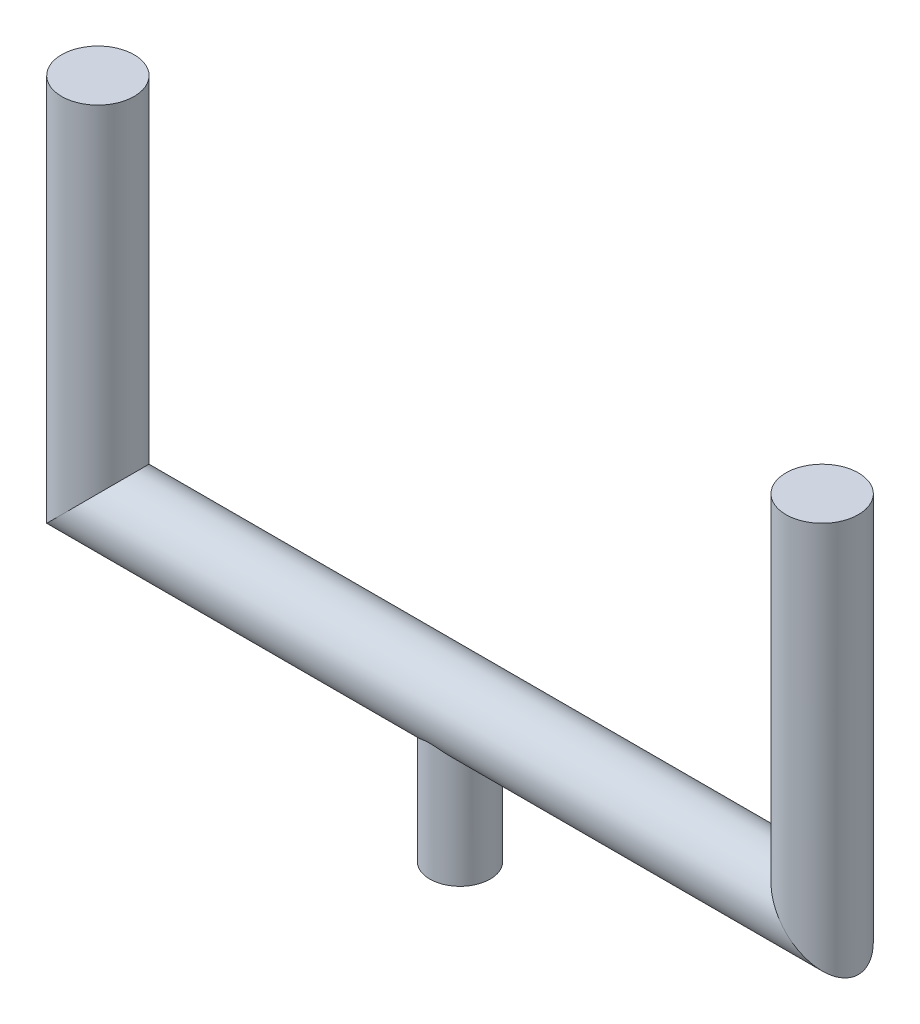
SolidWorks part; units mm, degrees
ref_plane "前视基准面" through (0, 0, 0) normal (0, 0, 1) x (1, 0, 0)
ref_plane "上视基准面" through (0, 0, 0) normal (0, 1, 0) x (1, 0, 0)
ref_plane "右视基准面" through (0, 0, 0) normal (1, 0, 0) x (0, 0, -1)
other "Configuration Table"
sketch "草图1" plane through (0, 0, 0) normal (0, 1, 0) x (1, 0, 0)
  circle A0 centre (0, 0) radius 3
sketch "草图2" plane through (0, 0, 0) normal (0, 0, 1) x (1, 0, 0)
  line L0 (0, 0) -> (0, -30)
  line L1 (0, -30) -> (60, -30)
  line L2 (30, -30) -> (30, 11.9626) construction
  line L3 (60, 0) -> (60, -30)
  dimension "D1" = 30
  dimension "D2" = 30
sweep "扫描1" add profiles "草图1" path "草图2"
ref_point "点1"
ref_axis "基准轴1" through (0, -33, 0) along (0, 1, 0)
ref_plane "基准面1" through (30, -30.1502, 0) normal (0, 1, 0) x (1, 0, 0)
sketch "草图4" plane through (30, -30.1502, 0) normal (0, 1, 0) x (1, 0, 0)
  circle A0 centre (0, 0) radius 2.5
extrude "凸台-拉伸1" add sketch "草图4" against normal blind 11.25
